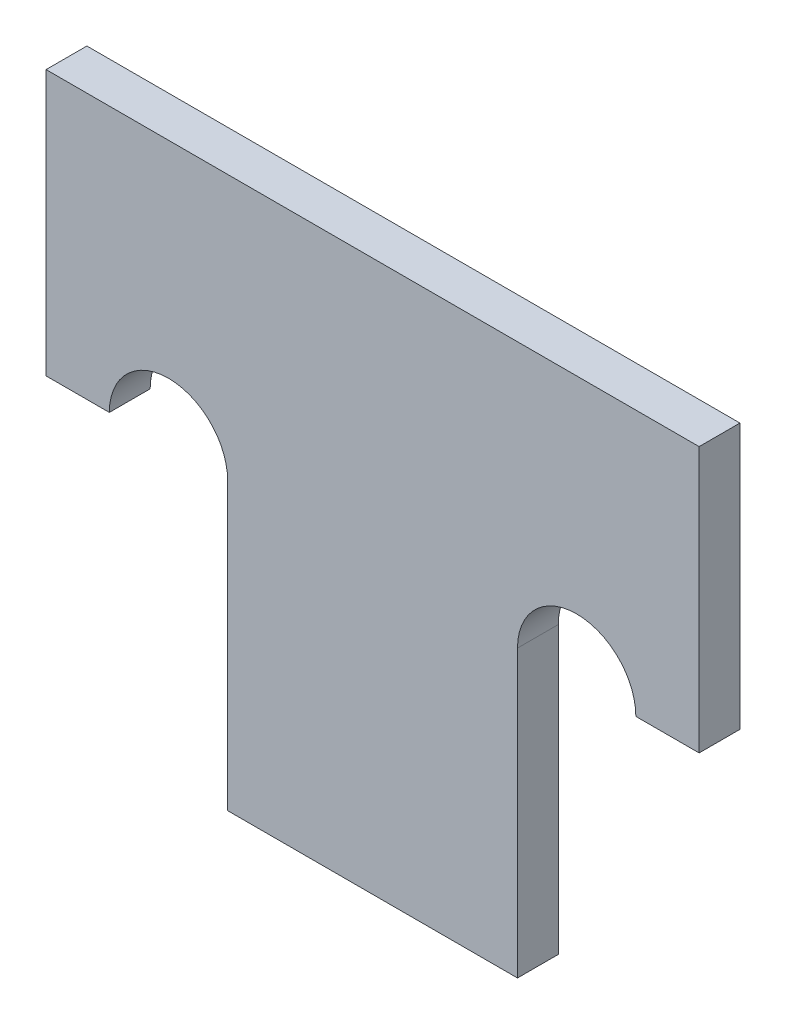
SolidWorks part; units mm, degrees
material "7075-T6 (SN)"
ref_plane "Front Plane" through (0, 0, 0) normal (0, 0, 1) x (1, 0, 0)
ref_plane "Top Plane" through (0, 0, 0) normal (0, 1, 0) x (1, 0, 0)
ref_plane "Right Plane" through (0, 0, 0) normal (1, 0, 0) x (0, 0, -1)
sketch "Sketch1" plane through (0, 0, 0) normal (0, 0, 1) x (1, 0, 0)
  line L0 (-20.32, 0.635) -> (20.32, 0.635) construction
  line L1 (-20.32, -17.145) -> (20.32, -17.145)
  line L2 (-20.32, -17.145) -> (-20.32, 17.145)
  line L3 (-20.32, 17.145) -> (20.32, 17.145)
  line L4 (20.32, -17.145) -> (20.32, 17.145)
  line L5 (-20.32, -17.145) -> (20.32, 17.145) construction
  line L6 (-20.32, 17.145) -> (20.32, -17.145) construction
  line L7 (0, 5.8923) -> (0, -3.1789) construction
  circle A0 centre (12.7, 0.635) radius 3.175
  circle A1 centre (-12.7, 0.635) radius 3.175
  point P0 (0, 0)
  dimension "D5" = 6.35
  dimension "D1" = 25.4
  dimension "D3" = 34.29
  dimension "D4" = 16.51
  dimension "D6" = 40.64
extrude "Boss-Extrude1" add sketch "Sketch1" along normal blind 2.54
sketch "Sketch2" plane through (0, 0, 0) normal (0, 0, 1) x (1, 0, 0)
  line L0 (0, -10.4784) -> (0, 10.4784) construction
  line L1 (9.017, 0.635) -> (9.017, -17.145)
  line L2 (-20.32, -17.145) -> (20.32, -17.145) construction
  line L4 (16.383, 0.635) -> (20.32, 0.635)
  line L6 (-9.017, 0.635) -> (-9.017, -17.145)
  line L20 (20.32, -17.145) -> (20.32, 17.145) construction
  line L22 (-16.383, 0.635) -> (-20.32, 0.635)
  line L23 (-20.32, 17.145) -> (-20.32, -17.145) construction
  line L24 (-20.32, 0.635) -> (-20.32, -17.145)
  line L25 (-20.32, -17.145) -> (-9.017, -17.145)
  line L26 (20.32, -17.145) -> (20.32, 0.635)
  line L27 (9.017, -17.145) -> (20.32, -17.145)
  arc A0 (16.383, 0.635) -> (9.017, 0.635) centre (12.7, 0.635) ccw
  circle A1 centre (12.7, 0.635) radius 3.175 construction
  arc A2 (-16.383, 0.635) -> (-9.017, 0.635) centre (-12.7, 0.635) cw
  dimension "D1" = 0.508
extrude "Cut-Extrude1" cut sketch "Sketch2" along normal up to surface (2.54 mm away) up to face at (0, 0, 2.54)
